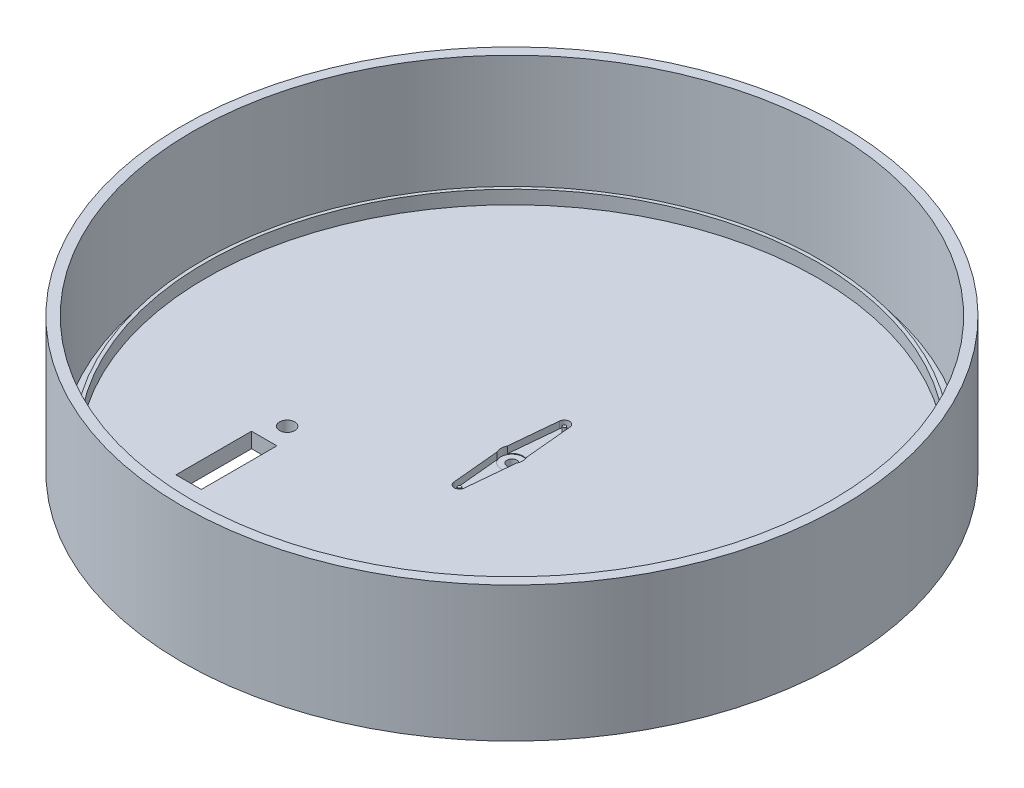
SolidWorks part; units mm, degrees
note: The reader was unsure of these and kept them because the rebuilt part matched: shared geometry of "Sketch9<4>".
material "ABS"
ref_plane "Ön Düzlem" through (0, 0, 0) normal (0, 0, 1) x (1, 0, 0)
ref_plane "Üst Düzlem" through (0, 0, 0) normal (0, 1, 0) x (1, 0, 0)
ref_plane "Sağ Düzlem" through (0, 0, 0) normal (1, 0, 0) x (0, 0, -1)
sketch "Sketch3" plane through (0, 0, 0) normal (0, 1, 0) x (1, 0, 0)
  circle A0 centre (0, 0) radius 97.5
  dimension "D1" = 195
extrude "Boss-Extrude3" add sketch "Sketch3" along normal blind 40
shell "Shell4" thickness 3
sketch "Sketch4" plane through (0, 4.5, 0) normal (0, 1, 0) x (1, 0, 0)
  line L0 (0, -20.8242) -> (0, 20.8242) construction
  line L1 (2.8699, 1.5252) -> (1.5432, 15.645)
  line L2 (-2.8699, 1.5252) -> (-1.5432, 15.645)
  line L3 (0, 0) -> (-4.5635, 0) construction
  line L4 (-2.8699, -1.5252) -> (-1.5432, -15.645)
  line L5 (2.8699, -1.5252) -> (1.5432, -15.645)
  arc A0 (-2.8699, 1.5252) -> (-2.8699, -1.5252) centre (0, 0) ccw
  arc A2 (1.5432, 15.645) -> (-1.5432, 15.645) centre (0, 15.5) ccw
  arc A3 (1.5432, -15.645) -> (-1.5432, -15.645) centre (0, -15.5) cw
  arc A5 (2.8699, -1.5252) -> (2.8699, 1.5252) centre (0, 0) ccw
  dimension "D1" = 6.5
  dimension "D3" = 15.5
  dimension "D4" = 3.1
extrude "Cut-Extrude1" cut sketch "Sketch4" against normal blind 2
sketch "Sketch5" plane through (0, 0, 0) normal (0, -1, 0) x (1, 0, 0)
  circle A0 centre (0, 0) radius 1.5
extrude "Cut-Extrude2" cut sketch "Sketch5" against normal up to next
sketch "Sketch6" plane through (0, 2.5, 0) normal (0, 1, 0) x (1, 0, 0)
  circle A0 centre (0, 0) radius 3.25
extrude "Cut-Extrude3" cut sketch "Sketch6" against normal blind 0.2
sketch "Sketch7" plane through (0, 2.5, 0) normal (0, 1, 0) x (1, 0, 0)
  circle A0 centre (0, 15.5) radius 0.48
  circle A1 centre (0, -15.5) radius 0.48
extrude "Boss-Extrude4" add sketch "Sketch7" along normal blind 1.5
sketch "Sketch8" plane through (0, 4.5, 0) normal (0, 1, 0) x (1, 0, 0)
  circle A0 centre (0, 0) radius 90.5
  circle A1 centre (0, 0) radius 91.5
extrude "Boss-Extrude5" add sketch "Sketch8" along normal blind 4
sketch "Sketch9" plane through (0, 0, 0) normal (0, -1, 0) x (1, 0, 0)
  line L0 (37, 32.5373) -> (44.5, 32.5373)
  line L1 (0, 0) -> (0, 152.8926) construction
  line L12 (20, 45) -> (-20, 45) construction
  line L13 (-37, 32.5373) -> (-37, 54.8973)
  line L14 (37, 32.5373) -> (37, 54.8973)
  line L16 (37, 54.8973) -> (44.5, 54.8973)
  line L42 (44.5, 54.8973) -> (44.5, 32.5373)
  line L43 (-37, 54.8973) -> (-44.5, 54.8973)
  line L44 (-44.5, 54.8973) -> (-44.5, 32.5373)
  line L45 (-37, 32.5373) -> (-44.5, 32.5373)
  circle A0 centre (40.5, 26) radius 2.25
  circle A1 centre (40.5, 64) radius 2.25
  circle A2 centre (-40.5, 64) radius 2.25
  circle A3 centre (-40.5, 26) radius 2.25
  dimension "D1" = 40.5
  dimension "D3" = 4.5
  dimension "D2" = 19
  dimension "D5" = 45
  dimension "D6" = 7.5
  dimension "D7" = 22.36
  dimension "D8" = 6.5373
  dimension "D9" = 3.5
extrude "Cut-Extrude12" cut sketch "Sketch9" against normal up to next contours A0 | A1 | A2 | A3
extrude "Cut-Extrude13" cut sketch "Sketch9<4>" against normal up to next contours L42 L16 L14 L0 | L44 L45 L13 L43
sketch "Sketch9<4>" plane through (0, 0, 0) normal (0, -1, 0) x (1, 0, 0) same geometry as "Sketch9"
